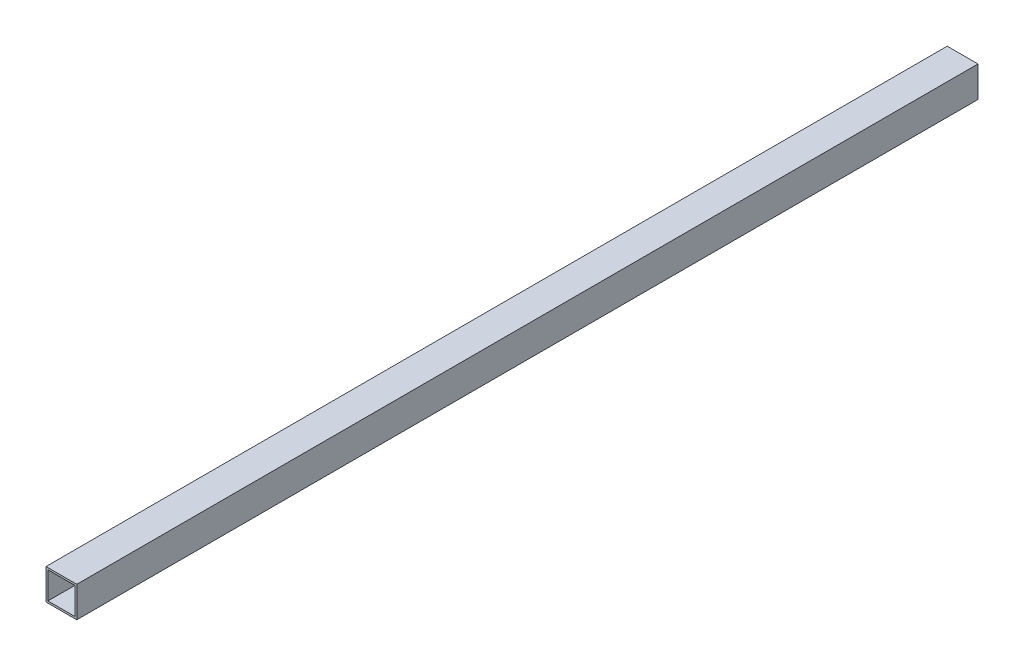
SolidWorks part; units mm, degrees
material "ALUMINUM 6061-T6"
ref_plane "Front Plane" through (0, 0, 0) normal (0, 0, 1) x (1, 0, 0)
ref_plane "Top Plane" through (0, 0, 0) normal (0, 1, 0) x (1, 0, 0)
ref_plane "Right Plane" through (0, 0, 0) normal (1, 0, 0) x (0, 0, -1)
sketch "Sketch1" plane through (0, 0, 0) normal (0, 0, 1) x (1, 0, 0)
  line L0 (11.1125, -11.1125) -> (11.1125, 11.1125)
  line L1 (-12.7, -12.7) -> (12.7, -12.7)
  line L2 (-12.7, -12.7) -> (-12.7, 12.7)
  line L3 (-12.7, 12.7) -> (12.7, 12.7)
  line L4 (12.7, -12.7) -> (12.7, 12.7)
  line L5 (-12.7, -12.7) -> (12.7, 12.7) construction
  line L6 (-12.7, 12.7) -> (12.7, -12.7) construction
  line L7 (-11.1125, 11.1125) -> (11.1125, 11.1125)
  line L8 (-11.1125, -11.1125) -> (-11.1125, 11.1125)
  line L9 (-11.1125, -11.1125) -> (11.1125, -11.1125)
  point P0 (0, 0)
  dimension "D1" = 25.4
  dimension "D2" = 25.4
  dimension "D3" = 1.5875
extrude "Boss-Extrude1" add sketch "Sketch1" along normal mid plane 743.458
